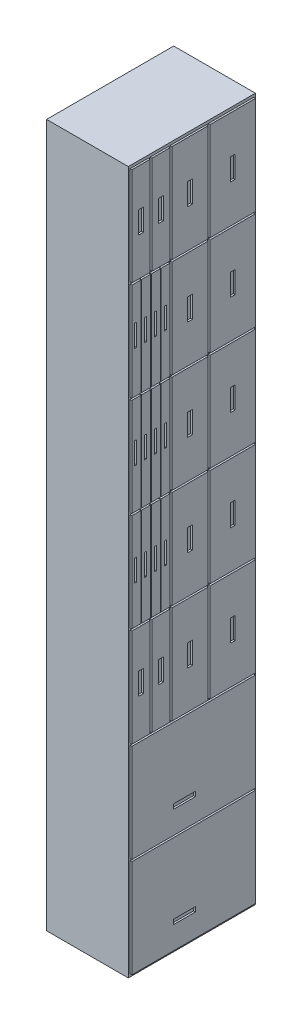
SolidWorks part; units mm, degrees
ref_plane "Front Plane" through (0, 0, 0) normal (0, 0, 1) x (1, 0, 0)
ref_plane "Top Plane" through (0, 0, 0) normal (0, 1, 0) x (1, 0, 0)
ref_plane "Right Plane" through (0, 0, 0) normal (1, 0, 0) x (0, 0, -1)
sketch "Sketch1" plane through (0, 0, 0) normal (0, 0, 1) x (1, 0, 0)
  line L0 (313.062, 4179.9863) -> (-136.938, 4179.9863)
  line L1 (-136.938, 4179.9863) -> (-136.938, 309.9863)
  line L2 (-136.938, 309.9863) -> (313.062, 309.9863)
  line L5 (313.062, 309.9863) -> (313.062, 4179.9863)
  dimension "D1" = 450
  dimension "D2" = 3870
extrude "Boss-Extrude1" add sketch "Sketch1" along normal blind 700
sketch "Sketch3" plane through (313.062, 0, 0) normal (1, 0, 0) x (0, 0, -1)
  line L0 (-555, 2184.9863) -> (-565, 2184.9863)
  line L1 (-690, 324.9863) -> (-10, 324.9863)
  line L2 (-690, 324.9863) -> (-690, 864.9863)
  line L3 (-690, 864.9863) -> (-10, 864.9863)
  line L4 (-10, 324.9863) -> (-10, 864.9863)
  line L5 (-700, 309.9863) -> (0, 309.9863) construction
  line L6 (-690, 874.9863) -> (-10, 874.9863)
  line L11 (-690, 874.9863) -> (-690, 1414.9863)
  line L12 (-690, 1414.9863) -> (-10, 1414.9863)
  line L13 (-10, 874.9863) -> (-10, 1414.9863)
  line L18 (-260, 1424.9863) -> (-10, 1424.9863)
  line L19 (-260, 1424.9863) -> (-260, 1964.9863)
  line L20 (-260, 1964.9863) -> (-10, 1964.9863)
  line L21 (-10, 1424.9863) -> (-10, 1964.9863)
  line L22 (-700, 309.9863) -> (-700, 4179.9863) construction
  line L23 (0, 309.9863) -> (0, 4179.9863) construction
  line L24 (-270, 2514.9863) -> (-470, 2514.9863)
  line L25 (-270, 1964.9863) -> (-470, 1964.9863)
  line L26 (-270, 2514.9863) -> (-270, 1974.9863)
  line L27 (-470, 2514.9863) -> (-470, 1974.9863)
  line L28 (-383, 2304.9863) -> (-357, 2304.9863)
  line L29 (-533.5, 1974.9863) -> (-583.5, 1974.9863)
  line L30 (-270, 1964.9863) -> (-270, 1424.9863)
  line L31 (-270, 1424.9863) -> (-470, 1424.9863)
  line L32 (-470, 1964.9863) -> (-470, 1424.9863)
  line L33 (-480, 1424.9863) -> (-580, 1424.9863)
  line L34 (-480, 1424.9863) -> (-480, 1964.9863)
  line L35 (-480, 1964.9863) -> (-580, 1964.9863)
  line L36 (-543, 1634.9863) -> (-517, 1634.9863)
  line L37 (-543, 1634.9863) -> (-543, 1754.9863)
  line L38 (-543, 1754.9863) -> (-517, 1754.9863)
  line L39 (-517, 1634.9863) -> (-517, 1754.9863)
  line L40 (-580, 1424.9863) -> (-580, 1964.9863)
  line L41 (-590, 1424.9863) -> (-690, 1424.9863)
  line L42 (-590, 1424.9863) -> (-590, 1964.9863)
  line L43 (-590, 1964.9863) -> (-690, 1964.9863)
  line L44 (-383, 1634.9863) -> (-357, 1634.9863)
  line L45 (-383, 1634.9863) -> (-383, 1754.9863)
  line L46 (-383, 1754.9863) -> (-357, 1754.9863)
  line L47 (-357, 1634.9863) -> (-357, 1754.9863)
  line L48 (-461.6648, 475.8892) -> (-340.5919, 475.8892)
  line L49 (-461.6648, 450.0868) -> (-340.5919, 450.0868)
  line L50 (-461.6648, 475.8892) -> (-461.6648, 450.0868)
  line L51 (-340.5919, 475.8892) -> (-340.5919, 450.0868)
  line L52 (-148, 1634.9863) -> (-122, 1634.9863)
  line L53 (-148, 1634.9863) -> (-148, 1754.9863)
  line L54 (-555, 2184.9863) -> (-555, 2304.9863)
  line L55 (-148, 1754.9863) -> (-122, 1754.9863)
  line L56 (-461.6648, 1025.8892) -> (-340.5919, 1025.8892)
  line L57 (-461.6648, 1000.0868) -> (-340.5919, 1000.0868)
  line L58 (-461.6648, 1025.8892) -> (-461.6648, 1000.0868)
  line L59 (-340.5919, 1025.8892) -> (-340.5919, 1000.0868)
  line L60 (-690, 1424.9863) -> (-690, 1964.9863)
  line L61 (-653, 1634.9863) -> (-627, 1634.9863)
  line L62 (-653, 1634.9863) -> (-653, 1754.9863)
  line L63 (-653, 1754.9863) -> (-627, 1754.9863)
  line L64 (-627, 1634.9863) -> (-627, 1754.9863)
  line L65 (-357, 2184.9863) -> (-357, 2304.9863)
  line L66 (-383, 2184.9863) -> (-383, 2304.9863)
  line L67 (-383, 2184.9863) -> (-357, 2184.9863)
  line L68 (-270, 1974.9863) -> (-470, 1974.9863)
  line L69 (-480, 1974.9863) -> (-530, 1974.9863)
  line L70 (-480, 1974.9863) -> (-480, 2514.9863)
  line L71 (-480, 2514.9863) -> (-530, 2514.9863)
  line L72 (-530, 1974.9863) -> (-530, 2514.9863)
  line L73 (-583.5, 1974.9863) -> (-583.5, 2514.9863)
  line L74 (-533.5, 1974.9863) -> (-533.5, 2514.9863)
  line L75 (-533.5, 2514.9863) -> (-583.5, 2514.9863)
  line L76 (-587, 1974.9863) -> (-637, 1974.9863)
  line L77 (-637, 1974.9863) -> (-637, 2514.9863)
  line L78 (-587, 1974.9863) -> (-587, 2514.9863)
  line L79 (-587, 2514.9863) -> (-637, 2514.9863)
  line L80 (-122, 1634.9863) -> (-122, 1754.9863)
  line L81 (-260, 1974.9863) -> (-10, 1974.9863)
  line L82 (-260, 1974.9863) -> (-260, 2514.9863)
  line L83 (-148, 2184.9863) -> (-148, 2304.9863)
  line L84 (-640.5, 1974.9863) -> (-690.5, 1974.9863)
  line L85 (-690.5, 1974.9863) -> (-690.5, 2514.9863)
  line L86 (-640.5, 1974.9863) -> (-640.5, 2514.9863)
  line L87 (-640.5, 2514.9863) -> (-690.5, 2514.9863)
  line L88 (-148, 2184.9863) -> (-122, 2184.9863)
  line L89 (-122, 2184.9863) -> (-122, 2304.9863)
  line L90 (-148, 2304.9863) -> (-122, 2304.9863)
  line L91 (-10, 1974.9863) -> (-10, 2514.9863)
  line L92 (-260, 2514.9863) -> (-10, 2514.9863)
  line L93 (-270, 3064.9863) -> (-470, 3064.9863)
  line L94 (-270, 3064.9863) -> (-270, 2524.9863)
  line L95 (-470, 3064.9863) -> (-470, 2524.9863)
  line L96 (-383, 2854.9863) -> (-357, 2854.9863)
  line L97 (-357, 2734.9863) -> (-357, 2854.9863)
  line L98 (-383, 2734.9863) -> (-383, 2854.9863)
  line L99 (-383, 2734.9863) -> (-357, 2734.9863)
  line L100 (-270, 2524.9863) -> (-470, 2524.9863)
  line L101 (-260, 2524.9863) -> (-10, 2524.9863)
  line L102 (-260, 2524.9863) -> (-260, 3064.9863)
  line L103 (-148, 2734.9863) -> (-148, 2854.9863)
  line L104 (-148, 2734.9863) -> (-122, 2734.9863)
  line L105 (-122, 2734.9863) -> (-122, 2854.9863)
  line L106 (-148, 2854.9863) -> (-122, 2854.9863)
  line L107 (-10, 2524.9863) -> (-10, 3064.9863)
  line L108 (-260, 3064.9863) -> (-10, 3064.9863)
  line L109 (-270, 3614.9863) -> (-470, 3614.9863)
  line L110 (-270, 3614.9863) -> (-270, 3074.9863)
  line L111 (-470, 3614.9863) -> (-470, 3074.9863)
  line L112 (-383, 3404.9863) -> (-357, 3404.9863)
  line L113 (-357, 3284.9863) -> (-357, 3404.9863)
  line L114 (-383, 3284.9863) -> (-383, 3404.9863)
  line L115 (-383, 3284.9863) -> (-357, 3284.9863)
  line L116 (-270, 3074.9863) -> (-470, 3074.9863)
  line L117 (-260, 3074.9863) -> (-10, 3074.9863)
  line L118 (-260, 3074.9863) -> (-260, 3614.9863)
  line L119 (-148, 3284.9863) -> (-148, 3404.9863)
  line L120 (-148, 3284.9863) -> (-122, 3284.9863)
  line L121 (-122, 3284.9863) -> (-122, 3404.9863)
  line L122 (-148, 3404.9863) -> (-122, 3404.9863)
  line L123 (-10, 3074.9863) -> (-10, 3614.9863)
  line L124 (-260, 3614.9863) -> (-10, 3614.9863)
  line L125 (-480, 2524.9863) -> (-480, 3064.9863)
  line L126 (-480, 3064.9863) -> (-530, 3064.9863)
  line L127 (-530, 2524.9863) -> (-530, 3064.9863)
  line L128 (-583.5, 2524.9863) -> (-583.5, 3064.9863)
  line L129 (-533.5, 2524.9863) -> (-533.5, 3064.9863)
  line L130 (-533.5, 3064.9863) -> (-583.5, 3064.9863)
  line L131 (-637, 2524.9863) -> (-637, 3064.9863)
  line L132 (-587, 2524.9863) -> (-587, 3064.9863)
  line L133 (-587, 3064.9863) -> (-637, 3064.9863)
  line L134 (-690.5, 2524.9863) -> (-690.5, 3064.9863)
  line L135 (-640.5, 2524.9863) -> (-640.5, 3064.9863)
  line L136 (-640.5, 3064.9863) -> (-690.5, 3064.9863)
  line L137 (-533.5, 2524.9863) -> (-583.5, 2524.9863)
  line L138 (-587, 2524.9863) -> (-637, 2524.9863)
  line L139 (-640.5, 2524.9863) -> (-690.5, 2524.9863)
  line L140 (-480, 2524.9863) -> (-530, 2524.9863)
  line L141 (-480, 3074.9863) -> (-480, 3614.9863)
  line L142 (-480, 3614.9863) -> (-530, 3614.9863)
  line L143 (-530, 3074.9863) -> (-530, 3614.9863)
  line L144 (-583.5, 3074.9863) -> (-583.5, 3614.9863)
  line L145 (-533.5, 3074.9863) -> (-533.5, 3614.9863)
  line L146 (-533.5, 3614.9863) -> (-583.5, 3614.9863)
  line L147 (-637, 3074.9863) -> (-637, 3614.9863)
  line L148 (-587, 3074.9863) -> (-587, 3614.9863)
  line L149 (-587, 3614.9863) -> (-637, 3614.9863)
  line L150 (-690.5, 3074.9863) -> (-690.5, 3614.9863)
  line L151 (-640.5, 3074.9863) -> (-640.5, 3614.9863)
  line L152 (-640.5, 3614.9863) -> (-690.5, 3614.9863)
  line L153 (-533.5, 3074.9863) -> (-583.5, 3074.9863)
  line L154 (-587, 3074.9863) -> (-637, 3074.9863)
  line L155 (-640.5, 3074.9863) -> (-690.5, 3074.9863)
  line L156 (-480, 3074.9863) -> (-530, 3074.9863)
  line L157 (-260, 3624.9863) -> (-260, 4164.9863)
  line L158 (-270, 4164.9863) -> (-270, 3624.9863)
  line L159 (-470, 4164.9863) -> (-470, 3624.9863)
  line L160 (-480, 3624.9863) -> (-480, 4164.9863)
  line L161 (-543, 3834.9863) -> (-543, 3954.9863)
  line L162 (-543, 3954.9863) -> (-517, 3954.9863)
  line L163 (-517, 3834.9863) -> (-517, 3954.9863)
  line L164 (-580, 3624.9863) -> (-580, 4164.9863)
  line L165 (-590, 3624.9863) -> (-590, 4164.9863)
  line L166 (-383, 3834.9863) -> (-383, 3954.9863)
  line L167 (-383, 3954.9863) -> (-357, 3954.9863)
  line L168 (-357, 3834.9863) -> (-357, 3954.9863)
  line L169 (-148, 3834.9863) -> (-148, 3954.9863)
  line L170 (-148, 3954.9863) -> (-122, 3954.9863)
  line L171 (-690, 3624.9863) -> (-690, 4164.9863)
  line L172 (-653, 3834.9863) -> (-653, 3954.9863)
  line L173 (-653, 3954.9863) -> (-627, 3954.9863)
  line L174 (-627, 3834.9863) -> (-627, 3954.9863)
  line L175 (-122, 3834.9863) -> (-122, 3954.9863)
  line L176 (-590, 3624.9863) -> (-690, 3624.9863)
  line L177 (-480, 3624.9863) -> (-580, 3624.9863)
  line L178 (-270, 3624.9863) -> (-470, 3624.9863)
  line L179 (-260, 3624.9863) -> (-10, 3624.9863)
  line L180 (-260, 4164.9863) -> (-10, 4164.9863)
  line L181 (-270, 4164.9863) -> (-470, 4164.9863)
  line L182 (-480, 4164.9863) -> (-580, 4164.9863)
  line L183 (-590, 4164.9863) -> (-690, 4164.9863)
  line L184 (-543, 3834.9863) -> (-517, 3834.9863)
  line L185 (-653, 3834.9863) -> (-627, 3834.9863)
  line L186 (-383, 3834.9863) -> (-357, 3834.9863)
  line L187 (-148, 3834.9863) -> (-122, 3834.9863)
  line L188 (-10, 3624.9863) -> (-10, 4164.9863)
  line L189 (-500, 2184.9863) -> (-510, 2184.9863)
  line L190 (-500, 2184.9863) -> (-500, 2304.9863)
  line L191 (-500, 2304.9863) -> (-510, 2304.9863)
  line L192 (-510, 2184.9863) -> (-510, 2304.9863)
  line L193 (-555, 2304.9863) -> (-565, 2304.9863)
  line L194 (-565, 2184.9863) -> (-565, 2304.9863)
  line L195 (-610, 2184.9863) -> (-620, 2184.9863)
  line L196 (-610, 2184.9863) -> (-610, 2304.9863)
  line L197 (-610, 2304.9863) -> (-620, 2304.9863)
  line L198 (-620, 2184.9863) -> (-620, 2304.9863)
  line L199 (-665, 2184.9863) -> (-675, 2184.9863)
  line L200 (-665, 2184.9863) -> (-665, 2304.9863)
  line L201 (-665, 2304.9863) -> (-675, 2304.9863)
  line L202 (-675, 2184.9863) -> (-675, 2304.9863)
  line L203 (-555, 2744.9863) -> (-565, 2744.9863)
  line L204 (-555, 2744.9863) -> (-555, 2864.9863)
  line L205 (-555, 2864.9863) -> (-565, 2864.9863)
  line L206 (-565, 2744.9863) -> (-565, 2864.9863)
  line L207 (-610, 2744.9863) -> (-620, 2744.9863)
  line L208 (-610, 2744.9863) -> (-610, 2864.9863)
  line L209 (-610, 2864.9863) -> (-620, 2864.9863)
  line L210 (-620, 2744.9863) -> (-620, 2864.9863)
  line L211 (-665, 2744.9863) -> (-675, 2744.9863)
  line L212 (-665, 2744.9863) -> (-665, 2864.9863)
  line L213 (-665, 2864.9863) -> (-675, 2864.9863)
  line L214 (-675, 2744.9863) -> (-675, 2864.9863)
  line L215 (-555, 3304.9863) -> (-565, 3304.9863)
  line L216 (-555, 3304.9863) -> (-555, 3424.9863)
  line L217 (-555, 3424.9863) -> (-565, 3424.9863)
  line L218 (-565, 3304.9863) -> (-565, 3424.9863)
  line L219 (-610, 3304.9863) -> (-620, 3304.9863)
  line L220 (-610, 3304.9863) -> (-610, 3424.9863)
  line L221 (-610, 3424.9863) -> (-620, 3424.9863)
  line L222 (-620, 3304.9863) -> (-620, 3424.9863)
  line L223 (-665, 3304.9863) -> (-675, 3304.9863)
  line L224 (-665, 3304.9863) -> (-665, 3424.9863)
  line L225 (-665, 3424.9863) -> (-675, 3424.9863)
  line L226 (-675, 3304.9863) -> (-675, 3424.9863)
  line L227 (-500, 2744.9863) -> (-510, 2744.9863)
  line L228 (-500, 2744.9863) -> (-500, 2864.9863)
  line L229 (-500, 2864.9863) -> (-510, 2864.9863)
  line L230 (-510, 2744.9863) -> (-510, 2864.9863)
  line L231 (-500, 3304.9863) -> (-510, 3304.9863)
  line L232 (-500, 3304.9863) -> (-500, 3424.9863)
  line L233 (-500, 3424.9863) -> (-510, 3424.9863)
  line L234 (-510, 3304.9863) -> (-510, 3424.9863)
  line L235 (-559.8587, 402.1875) -> (-559.8587, 789.309)
  text T0 "Locked\r\n with key" font "Century Gothic" height 50.05
  point P241 (0, 0)
  dimension "D1" = 540
  dimension "D2" = 10
  dimension "D3" = 15
  dimension "D4" = 250
  dimension "D6" = 10
  dimension "D7" = 200
  dimension "D5" = 10
  dimension "D8" = 100
  dimension "D9" = 10
  dimension "D10" = 10
  dimension "D11" = 10
  dimension "D12" = 37
  dimension "D13" = 26
  dimension "D14" = 26
  dimension "D15" = 540
  dimension "D16" = 26
  dimension "D17" = 87
  dimension "D18" = 112
  dimension "D19" = 4
  dimension "D20" = 3
  dimension "D21" = 100
  dimension "D22" = 10
  dimension "D23" = 10
  dimension "D24" = 120
  dimension "D25" = 26
  dimension "D26" = 210
  dimension "D27" = 37
  dimension "D28" = 2
  dimension "D29" = 20
  dimension "D30" = 4
  dimension "D31" = 50
  dimension "D32" = 4
  dimension "D33" = 3
extrude "Boss-Extrude3" add sketch "Sketch3" along normal blind 10
sketch "Sketch4" plane through (323.062, 0, 0) normal (1, 0, 0) x (0, 0, -1)
  text T0 "LOCKED with key" font "Century Gothic" height 40
  point P3 (0, 0)
sketch "Sketch5" plane through (323.062, 0, 0) normal (1, 0, 0) x (0, 0, -1)
  text T0 "LOCKED with key" font "Century Gothic" height 40
equation "\"Aa\"=540"
equation "\"D1@Sketch3\"=\"Aa\""
equation "\"D15@Sketch3\" = \"Aa\""
equation "\"Ab\"=10"
equation "\"D5@Sketch3\"=\"Ab\""
equation "\"D2@Sketch3\"=\"Ab\""
equation "\"D6@Sketch3\"=\"Ab\""
equation "\"D10@Sketch3\"=\"Ab\""
equation "\"D11@Sketch3\"=\"Ab\""
equation "\"D22@Sketch3\" = \"Ab\""
